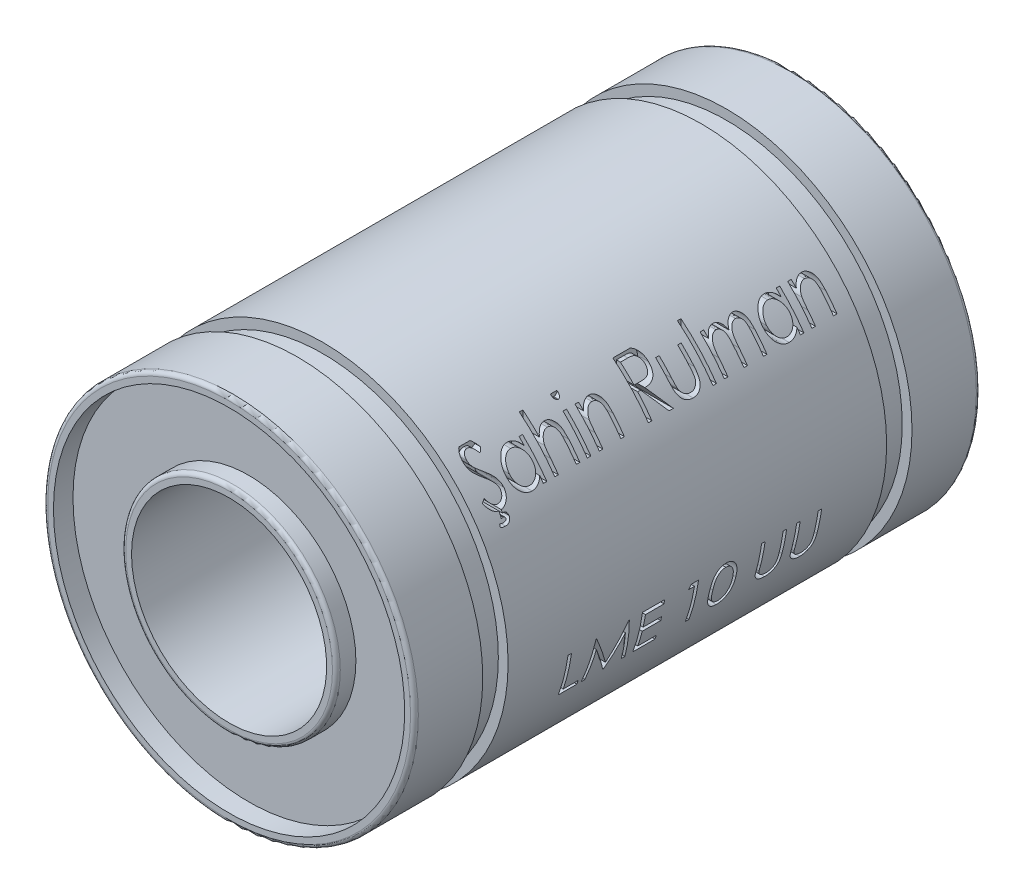
SolidWorks part; units mm, degrees
ref_plane "Front Plane" through (0, 0, 0) normal (0, 0, 1) x (1, 0, 0)
ref_plane "Top Plane" through (0, 0, 0) normal (0, 1, 0) x (1, 0, 0)
ref_plane "Right Plane" through (0, 0, 0) normal (1, 0, 0) x (0, 0, -1)
sketch "Sketch1" plane through (0, 0, 0) normal (0, 0, 1) x (1, 0, 0)
  circle A0 centre (0, 0) radius 9.5
  circle A1 centre (0, 0) radius 5
  dimension "D1" = 19
  dimension "D2" = 10
extrude "Boss-Extrude1" add sketch "Sketch1" along normal mid plane 29
sketch "Sketch2" plane through (0, 0, 0) normal (1, 0, 0) x (0, 0, -1)
  line L0 (-17.3437, 0) -> (17.7488, 0) construction
  line L1 (0, -11.1022) -> (0, 10.4762) construction
  line L2 (-11, 9) -> (-9.7, 9)
  line L3 (9.7, 9) -> (9.7, 10.4762)
  line L4 (11, 9) -> (11, 10.4762)
  line L5 (-11, 10.4762) -> (-9.7, 10.4762)
  line L6 (-17.3437, 9) -> (17.7488, 9) construction
  line L7 (-11, 9) -> (-11, 10.4762)
  line L8 (11, 10.4762) -> (9.7, 10.4762)
  line L9 (-9.7, 9) -> (-9.7, 10.4762)
  line L10 (11, 9) -> (9.7, 9)
  dimension "D1" = 9
revolve "Cut-Revolve1" cut sketch "Sketch2" angle 360 about L0
ref_plane "Plane1" through (11, 0, 0) normal (1, 0, 0) x (0, 0, -1)
sketch "Sketch3" plane through (11, 0, 0) normal (1, 0, 0) x (0, 0, -1)
  text T0 "Şahin Rulman\r\n\r\n   LME 10 UU" font "Century Gothic" height 2
extrude "Cut-Extrude1" cut sketch "Sketch3" against normal blind 5
sketch "Sketch4" plane through (0, 0, 14.5) normal (0, 0, 1) x (1, 0, 0)
  circle A0 centre (0, 0) radius 5.5
  circle A1 centre (0, 0) radius 9
extrude "Cut-Extrude2" cut sketch "Sketch4" against normal blind 1
mirror "Mirror1" about plane through (0, 0, 0) normal (0, 0, 1) of "Cut-Extrude2"
fillet "Fillet1" radius 0.2 4 edges at (5.5, 0, 14.5) (9.5, 0, 14.5) (5.5, 0, -14.5) (9.5, 0, -14.5)
